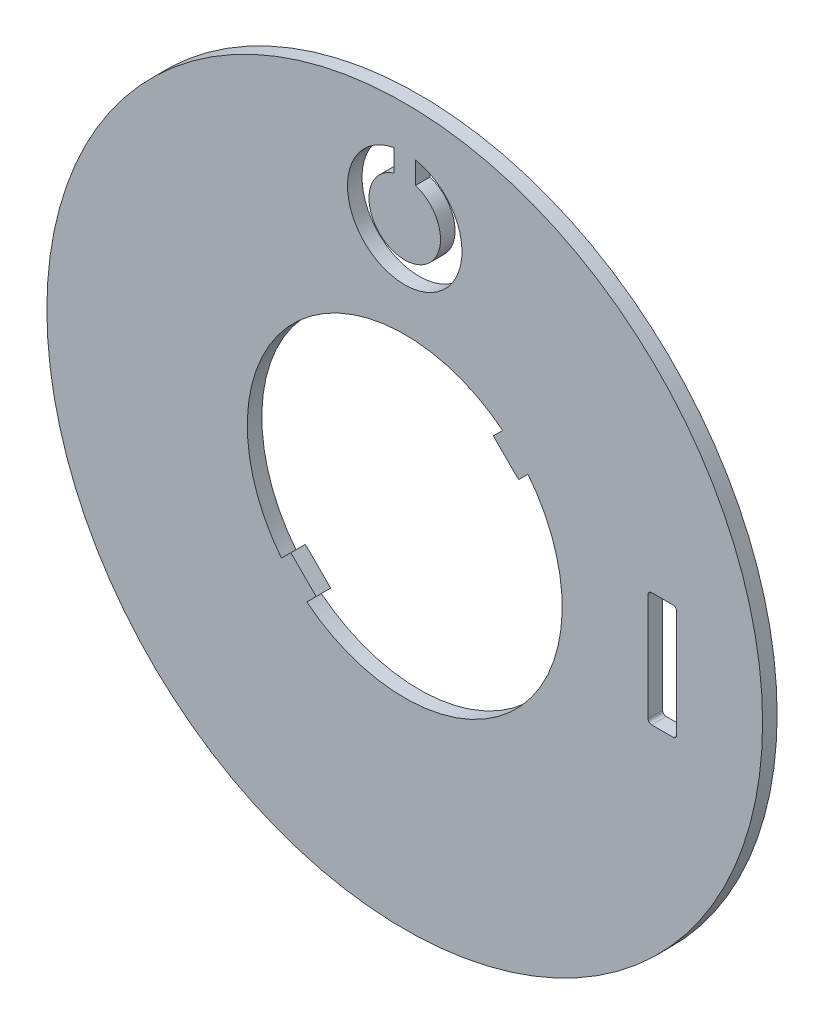
SolidWorks part; units mm, degrees
material "6061-T4 (SS)"
ref_plane "Front Plane" through (0, 0, 0) normal (0, 0, 1) x (1, 0, 0)
ref_plane "Top Plane" through (0, 0, 0) normal (0, 1, 0) x (1, 0, 0)
ref_plane "Right Plane" through (0, 0, 0) normal (1, 0, 0) x (0, 0, -1)
sketch "Sketch1" plane through (0, 0, 0) normal (0, 0, 1) x (1, 0, 0)
  line L28 (45.6621, 68.6943) -> (43.8943, 70.4621)
  line L29 (44.955, 67.9872) -> (45.6621, 68.6943)
  line L30 (43.1872, 69.755) -> (44.955, 67.9872)
  line L31 (43.8943, 70.4621) -> (43.1872, 69.755)
  line L32 (45.6621, 68.6943) -> (43.8943, 70.4621)
  line L33 (44.955, 67.9872) -> (45.6621, 68.6943)
  line L34 (43.1872, 69.755) -> (44.955, 67.9872)
  line L35 (43.8943, 70.4621) -> (43.1872, 69.755)
  line L36 (30.1057, 53.1379) -> (30.8128, 53.845)
  line L37 (28.3379, 54.9057) -> (30.1057, 53.1379)
  line L38 (29.045, 55.6128) -> (28.3379, 54.9057)
  line L39 (30.8128, 53.845) -> (29.045, 55.6128)
  line L40 (30.1057, 53.1379) -> (30.8128, 53.845)
  line L41 (28.3379, 54.9057) -> (30.1057, 53.1379)
  line L42 (29.045, 55.6128) -> (28.3379, 54.9057)
  line L43 (30.8128, 53.845) -> (29.045, 55.6128)
  circle A28 centre (37, 61.8) radius 25
  circle A29 centre (37, 61.8) radius 25
  circle A32 centre (37, 61.8) radius 11
  circle A33 centre (37, 61.8) radius 11
  dimension "D4" = 0
  dimension "D6" = 0
  dimension "D11" = 0
  dimension "D12" = 0
extrude "Boss-Extrude1" add sketch "Sketch1" along normal blind 1.016 contours A29 A33 L35 L32 L33 L40 L41 L42 | L35 L34 L33 L32 | L42 L41 L40 L43 region at (12.7071, 61.8, 0)
sketch "Sketch2" plane through (0, 0, 0) normal (0, 0, 1) x (1, 0, 0)
  line L0 (37, 72.8) -> (37, 86.8) construction
  line L1 (36.25, 82.1848) -> (36.25, 83.7291)
  line L2 (37.75, 83.7291) -> (37.75, 82.1848)
  line L3 (37.75, 82.957) -> (36.25, 82.957) construction
  line L4 (48, 61.8) -> (62, 61.8) construction
  line L8 (54.25, 57.8) -> (55.75, 57.8)
  line L9 (54, 58.05) -> (54, 65.55)
  line L10 (54.25, 65.8) -> (55.75, 65.8)
  line L11 (56, 58.05) -> (56, 65.55)
  line L12 (54, 57.8) -> (56, 65.8) construction
  line L13 (54, 65.8) -> (56, 57.8) construction
  arc A4 (36.25, 83.7291) -> (37.75, 83.7291) centre (37, 79.8) ccw
  arc A5 (36.25, 82.1848) -> (37.75, 82.1848) centre (37, 79.8) ccw
  arc A7 (55.75, 65.8) -> (56, 65.55) centre (55.75, 65.55) cw
  arc A8 (54, 65.55) -> (54.25, 65.8) centre (54.25, 65.55) cw
  arc A9 (54.25, 57.8) -> (54, 58.05) centre (54.25, 58.05) cw
  arc A10 (55.75, 57.8) -> (56, 58.05) centre (55.75, 58.05) ccw
  circle A11 centre (37, 61.8) radius 11 construction
  circle A12 centre (37, 61.8) radius 11
  circle A13 centre (37, 61.8) radius 25 construction
  circle A14 centre (37, 61.8) radius 25
  point P3 (37, 79.8)
  point P5 (55, 61.8)
  dimension "D2" = 1.5
  dimension "D3" = 4
  dimension "D7" = 0.25
  dimension "D4" = 2
  dimension "D5" = 8
  dimension "D6" = 1.5
extrude "Cut-Extrude1" cut sketch "Sketch2" along normal through all contours A5 L1 A4 L2 | L8 A10 L11 A7 L10 A8 L9 A9 region at (37, 77.1874, 0) region at (55, 61.8, 0)
